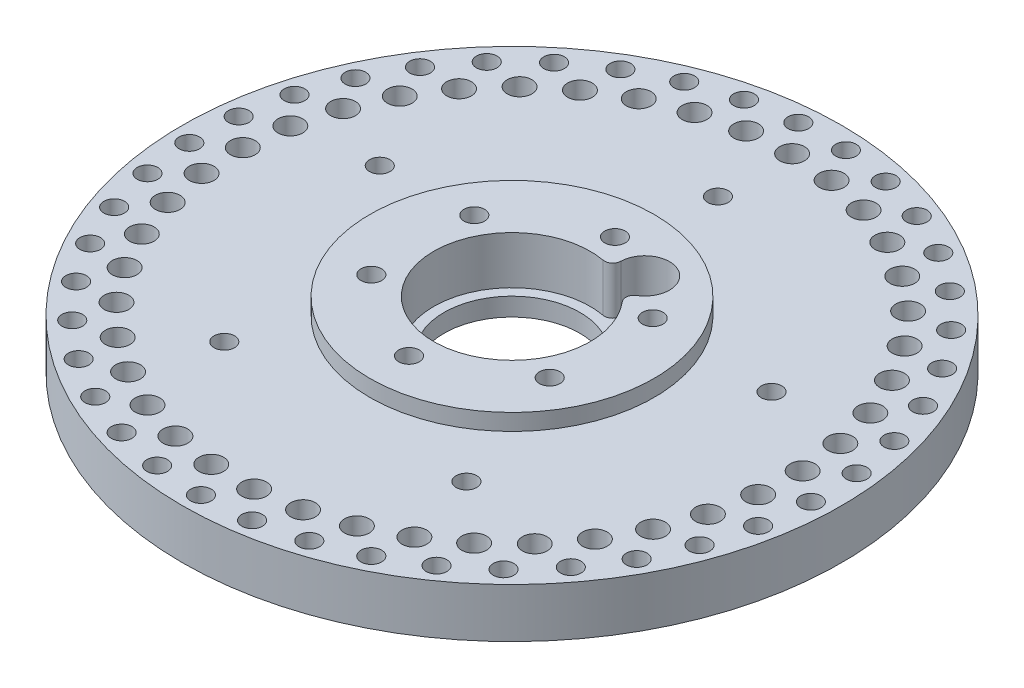
SolidWorks part; units mm, degrees
material "6061 Alloy"
ref_plane "Front Plane" through (0, 0, 0) normal (0, 0, 1) x (1, 0, 0)
ref_plane "Top Plane" through (0, 0, 0) normal (0, 1, 0) x (1, 0, 0)
ref_plane "Right Plane" through (0, 0, 0) normal (1, 0, 0) x (0, 0, -1)
sketch "Sketch1" plane through (0, 0, 0) normal (0, 1, 0) x (1, 0, 0)
  circle A0 centre (0, 0) radius 40
  dimension "D1" = 80
extrude "podstawa" add sketch "Sketch1" along normal blind 6
sketch "Sketch2" plane through (0, 6, 0) normal (0, 1, 0) x (1, 0, 0)
  circle A0 centre (0, 0) radius 9.5
  dimension "D1" = 19
extrude "gniazdo lozyska" cut sketch "Sketch2" against normal up to next and the other way through all
hole_wizard "walki cykloidy" positions "Sketch3" profile "Sketch5" hole size "Ø3.0" standard "DIN" end condition up to next
sketch "Sketch3" plane through (0, 6, 0) normal (0, 1, 0) x (1, 0, 0)
  line L0 (0, 34) -> (0, 40) construction
  circle A0 centre (0, 0) radius 40 construction
  point P0 (0, 34)
  point P15 (5.1901, 33.6015)
  point P16 (10.2585, 32.4155)
  point P17 (15.0865, 30.4696)
  point P18 (19.5608, 27.8096)
  point P19 (23.5767, 24.4977)
  point P20 (27.04, 20.6117)
  point P21 (29.8694, 16.2425)
  point P22 (31.9988, 11.4926)
  point P23 (33.3781, 6.4733)
  point P24 (33.9751, 1.3023)
  point P25 (33.7757, -3.8992)
  point P26 (32.7846, -9.0094)
  point P27 (31.0251, -13.9083)
  point P28 (28.5384, -18.4813)
  point P29 (25.3828, -22.6211)
  point P30 (21.6322, -26.2306)
  point P31 (17.3746, -29.2254)
  point P32 (12.7098, -31.5351)
  point P33 (7.747, -33.1056)
  point P34 (2.6027, -33.9002)
  point P35 (-2.6027, -33.9002)
  point P36 (-7.747, -33.1056)
  point P37 (-12.7098, -31.5351)
  point P38 (-17.3746, -29.2254)
  point P39 (-21.6322, -26.2306)
  point P40 (-25.3828, -22.6211)
  point P41 (-28.5384, -18.4813)
  point P42 (-31.0251, -13.9083)
  point P43 (-32.7846, -9.0094)
  point P44 (-33.7757, -3.8992)
  point P45 (-33.9751, 1.3023)
  point P46 (-33.3781, 6.4733)
  point P47 (-31.9988, 11.4926)
  point P48 (-29.8694, 16.2425)
  point P49 (-27.04, 20.6117)
  point P63 (-23.5767, 24.4977)
  point P64 (-19.5608, 27.8096)
  point P65 (-15.0865, 30.4696)
  point P66 (-10.2585, 32.4155)
  point P67 (-5.1901, 33.6015)
  dimension "D1" = 6
  dimension "D2" = 41
sketch "Sketch5" plane through (0, 6, -34) normal (1, 0, 0) x (0, 0, 1)
  line L0 (0, 0) -> (0, 6)
  line L1 (0, 6) -> (1.5, 6)
  line L2 (1.5, 6) -> (1.5, 0)
  line L5 (1.5, 0) -> (0, 0)
  line L11 (0, -6.35) -> (0, 107.95) construction
  dimension "Thru Hole Dia." = 3
  dimension "Thru Hole Depth" = 6
hole_wizard "Tap Drill for M3 Tap1" positions "Sketch7" profile "Sketch8" hole size "M3" standard "DIN" end condition up to next
sketch "Sketch7" plane through (0, 6, 0) normal (0, 1, 0) x (1, 0, 0)
  line L0 (0, 0) -> (0, 34)
  line L2 (0, 0) -> (5.1901, 33.6015)
  line L4 (5.1901, 33.6015) -> (0, 34)
  line L6 (3.2233, 41.9837) -> (0, 0)
  circle A0 centre (0, 0) radius 35.5
  circle A1 centre (0, 0) radius 40
  circle A3 centre (0, 0) radius 37.75 construction
  point P33 (2.8897, 37.6392)
  point P40 (8.6015, 36.757)
  point P41 (14.1116, 35.0132)
  point P42 (19.291, 32.4488)
  point P43 (24.0182, 29.1237)
  point P44 (28.1824, 25.116)
  point P45 (31.686, 20.5197)
  point P46 (34.447, 15.4423)
  point P47 (36.4006, 10.0031)
  point P48 (37.5009, 4.3293)
  point P49 (37.7223, -1.4459)
  point P50 (37.0595, -7.1873)
  point P51 (35.528, -12.7601)
  point P52 (33.1638, -18.0339)
  point P53 (30.0223, -22.885)
  point P54 (26.1771, -27.1997)
  point P55 (21.7183, -30.8768)
  point P56 (16.7504, -33.8302)
  point P57 (11.39, -35.9907)
  point P58 (5.7625, -37.3076)
  point P59 (0, -37.75)
  point P60 (-5.7625, -37.3076)
  point P61 (-11.39, -35.9907)
  point P62 (-16.7504, -33.8302)
  point P63 (-21.7183, -30.8768)
  point P64 (-26.1771, -27.1997)
  point P65 (-30.0223, -22.885)
  point P66 (-33.1638, -18.0339)
  point P67 (-35.528, -12.7601)
  point P68 (-37.0595, -7.1873)
  point P69 (-37.7223, -1.4459)
  point P70 (-37.5009, 4.3293)
  point P71 (-36.4006, 10.0031)
  point P72 (-34.447, 15.4423)
  point P73 (-31.686, 20.5197)
  point P74 (-28.1824, 25.116)
  point P75 (-24.0182, 29.1237)
  point P76 (-19.291, 32.4488)
  point P77 (-14.1116, 35.0132)
  point P78 (-8.6015, 36.757)
  point P79 (-2.8897, 37.6392)
  dimension "D1" = 80
  dimension "D2" = 71
  dimension "D3" = 75.5
  dimension "D4" = 41
sketch "Sketch8" plane through (-2.8897, 6, -37.6392) normal (1, 0, 0) x (0, 0, 1)
  line L0 (0, 0) -> (0, 6)
  line L1 (0, 6) -> (1.25, 6)
  line L2 (1.25, 6) -> (1.25, 0)
  line L5 (1.25, 0) -> (0, 0)
  line L11 (0, -6.35) -> (0, 107.95) construction
  dimension "Thru Hole Dia." = 2.5
  dimension "Thru Hole Depth" = 6
sketch "Sketch9" plane through (0, 0, 0) normal (0, 1, 0) x (1, 0, 0)
  circle A1 centre (0, 0) radius 9.5 construction
  circle A3 centre (0, 0) radius 8.25
  circle A4 centre (0, 0) radius 9.5
  dimension "D1" = 16.5
extrude "prog lozyska" add sketch "Sketch9" along normal blind 2.2
hole_wizard "Tap Drill for M3 Tap2" positions "Sketch10" profile "Sketch11" hole size "M3" standard "DIN" end condition up to next
sketch "Sketch10" plane through (0, 6, 0) normal (0, 1, 0) x (1, 0, 0)
  line L0 (0, 12.5) -> (0, 0)
  circle A0 centre (0, 12.5) radius 2.75
  circle A1 centre (0, 12.5) radius 3
  circle A3 centre (0, 0) radius 9.5 construction
  circle A4 centre (0, 0) radius 12.5
  point P0 (0, 12.5)
  point P16 (10.8253, 6.25)
  point P17 (10.8253, -6.25)
  point P45 (0, -12.5)
  point P46 (-10.8253, -6.25)
  point P47 (-10.8253, 6.25)
  dimension "D1" = 5.5
  dimension "D3" = 6
  dimension "D4" = 25
  dimension "D2" = 6
sketch "Sketch11" plane through (0, 6, -12.5) normal (1, 0, 0) x (0, 0, 1)
  line L0 (0, 0) -> (0, 6)
  line L1 (0, 6) -> (1.25, 6)
  line L2 (1.25, 6) -> (1.25, 0)
  line L5 (1.25, 0) -> (0, 0)
  line L11 (0, -6.35) -> (0, 107.95) construction
  dimension "Thru Hole Dia." = 2.5
  dimension "Thru Hole Depth" = 6
sketch "Sketch12" plane through (0, 6, 0) normal (0, 1, 0) x (1, 0, 0)
  line L0 (0, 12.5) -> (10.8253, 6.25) construction
  line L1 (0, 0) -> (9.7644, 16.9124) construction
  line L2 (4.75, 8.2272) -> (4.4, 7.621) construction
  circle A1 centre (5.9, 10.2191) radius 3
  circle A2 centre (0, 0) radius 9.5 construction
  dimension "D1" = 6
  dimension "D2" = 0.7
extrude "Cut-Extrude1" cut sketch "Sketch12" against normal up to surface (3.8 mm away) up to face at (0, 2.2, 9.5)
fillet "Fillet1" radius 1 2 edges at (6.1619, 4.1, -7.2306) (3.1809, 4.1, -8.9516)
hole_wizard "Tap Drill for M3 Tap3" positions "Sketch14" profile "Sketch15" hole size "M3" standard "DIN"
sketch "Sketch14" plane through (0, 6, 0) normal (0, 1, 0) x (1, 0, 0)
  point P0 (0, 25)
  point P9 (23.7764, 7.7254)
  point P10 (14.6946, -20.2254)
  point P11 (-14.6946, -20.2254)
  point P12 (-23.7764, 7.7254)
  dimension "D1" = 25
  dimension "D2" = 5
sketch "Sketch15" plane through (0, 6, -25) normal (1, 0, 0) x (0, 0, 1)
  line L0 (0, 0) -> (0, 6.7511)
  line L1 (0, 6.7511) -> (1.25, 6)
  line L2 (1.25, 6) -> (1.25, 0)
  line L5 (1.25, 0) -> (0, 0)
  line L10 (0, 6.7511) -> (-1.25, 6) construction
  line L11 (0, -6.35) -> (0, 107.95) construction
  dimension "Hole Dia." = 2.5
  dimension "Hole Depth" = 6
  dimension "Drill Angle" = 118
sketch "Sketch16" plane through (0, 6, 0) normal (0, 1, 0) x (1, 0, 0)
  circle A0 centre (0, 0) radius 17.25
  arc A1 (1.7203, 9.3429) -> (2.9011, 10.2996) centre (1.9014, 10.3264) ccw construction
  arc A2 (7.4692, 7.6622) -> (2.9011, 10.2996) centre (5.9, 10.2191) ccw construction
  arc A3 (7.4692, 7.6622) -> (7.231, 6.1613) centre (7.9922, 6.8099) ccw construction
  arc A4 (1.7203, 9.3429) -> (7.231, 6.1613) centre (0, 0) ccw construction
  circle A5 centre (10.8253, 6.25) radius 1.25 construction
  circle A6 centre (10.8253, -6.25) radius 1.25 construction
  circle A7 centre (0, -12.5) radius 1.25 construction
  circle A8 centre (-10.8253, -6.25) radius 1.25 construction
  circle A9 centre (-10.8253, 6.25) radius 1.25 construction
  circle A10 centre (0, 12.5) radius 1.25 construction
  arc A11 (1.7203, 9.3429) -> (2.9011, 10.2996) centre (1.9014, 10.3264) ccw
  arc A12 (7.4692, 7.6622) -> (2.9011, 10.2996) centre (5.9, 10.2191) ccw
  arc A13 (7.4692, 7.6622) -> (7.231, 6.1613) centre (7.9922, 6.8099) ccw
  arc A14 (1.7203, 9.3429) -> (7.231, 6.1613) centre (0, 0) ccw
  circle A15 centre (10.8253, 6.25) radius 1.25
  circle A16 centre (10.8253, -6.25) radius 1.25
  circle A17 centre (0, -12.5) radius 1.25
  circle A18 centre (-10.8253, -6.25) radius 1.25
  circle A19 centre (-10.8253, 6.25) radius 1.25
  circle A20 centre (0, 12.5) radius 1.25
  dimension "D1" = 34.5
extrude "Boss-Extrude1" add sketch "Sketch16" along normal blind 2
equation "\"D3@Sketch7\"=(\"D2@Sketch7\"+\"D1@Sketch7\")/2"
